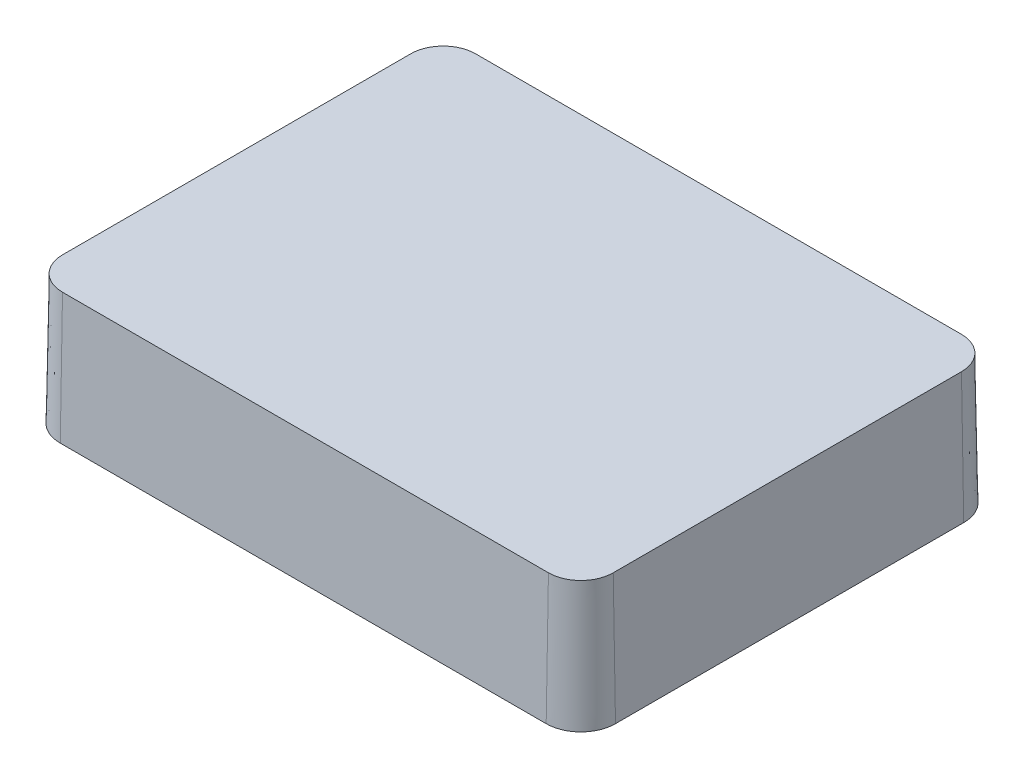
SolidWorks part; units mm, degrees
ref_plane "Front Plane" through (0, 0, 0) normal (0, 0, 1) x (1, 0, 0)
ref_plane "Top Plane" through (0, 0, 0) normal (0, 1, 0) x (1, 0, 0)
ref_plane "Right Plane" through (0, 0, 0) normal (1, 0, 0) x (0, 0, -1)
sketch "Sketch1" plane through (0, 0, 0) normal (0, 1, 0) x (1, 0, 0)
  line L1 (-7.5, -6.375) -> (7.5, -6.375)
  line L2 (-8.5, -5.375) -> (-8.5, 5.375)
  line L3 (-7.5, 6.375) -> (7.5, 6.375)
  line L4 (8.5, -5.375) -> (8.5, 5.375)
  line L5 (-8.5, -6.375) -> (8.5, 6.375) construction
  line L6 (-8.5, 6.375) -> (8.5, -6.375) construction
  arc A0 (-8.5, 5.375) -> (-7.5, 6.375) centre (-7.5, 5.375) cw
  arc A1 (8.5, 5.375) -> (7.5, 6.375) centre (7.5, 5.375) ccw
  arc A2 (8.5, -5.375) -> (7.5, -6.375) centre (7.5, -5.375) cw
  arc A3 (-7.5, -6.375) -> (-8.5, -5.375) centre (-7.5, -5.375) cw
  point P0 (0, 0)
  dimension "D3" = 1
  dimension "D1" = 17
  dimension "D2" = 12.75
extrude "Boss-Extrude1" add sketch "Sketch1" against normal blind 4 draft 1 draft outward yes
shell "Shell1" thickness 0.5 removed face at (0, -4, 0)
sketch "Sketch2" plane through (0, -0.5, 0) normal (0, -1, 0) x (1, 0, 0)
  line L0 (-0.6, 2.9308) -> (-0.6, 0.6)
  line L1 (-2.9308, 0.6) -> (-0.6, 0.6)
  line L2 (0, -55) -> (0, 55) construction
  line L3 (2.2, 0) -> (-2.2, 0) construction
  line L4 (-2.9308, -0.6) -> (-0.6, -0.6)
  line L5 (0.6, 2.9308) -> (0.6, 0.6)
  line L6 (-0.6, -0.6) -> (-0.6, -2.9308)
  line L7 (0.6, -0.6) -> (0.6, -2.9308)
  line L8 (0.6, -0.6) -> (2.9308, -0.6)
  line L9 (0.6, 0.6) -> (2.9308, 0.6)
  arc A0 (-2.9308, -0.6) -> (-0.6, -2.9308) centre (0, 0) ccw
  arc A1 (2.9308, 0.6) -> (0.6, 2.9308) centre (0, 0) ccw
  arc A2 (-0.6, 2.9308) -> (-2.9308, 0.6) centre (0, 0) ccw
  arc A3 (0.6, -2.9308) -> (2.9308, -0.6) centre (0, 0) ccw
  dimension "D1" = 0.6
  dimension "D2" = 0.6
extrude "Boss-Extrude2" add sketch "Sketch2" along normal blind 5.5 draft 1.5
